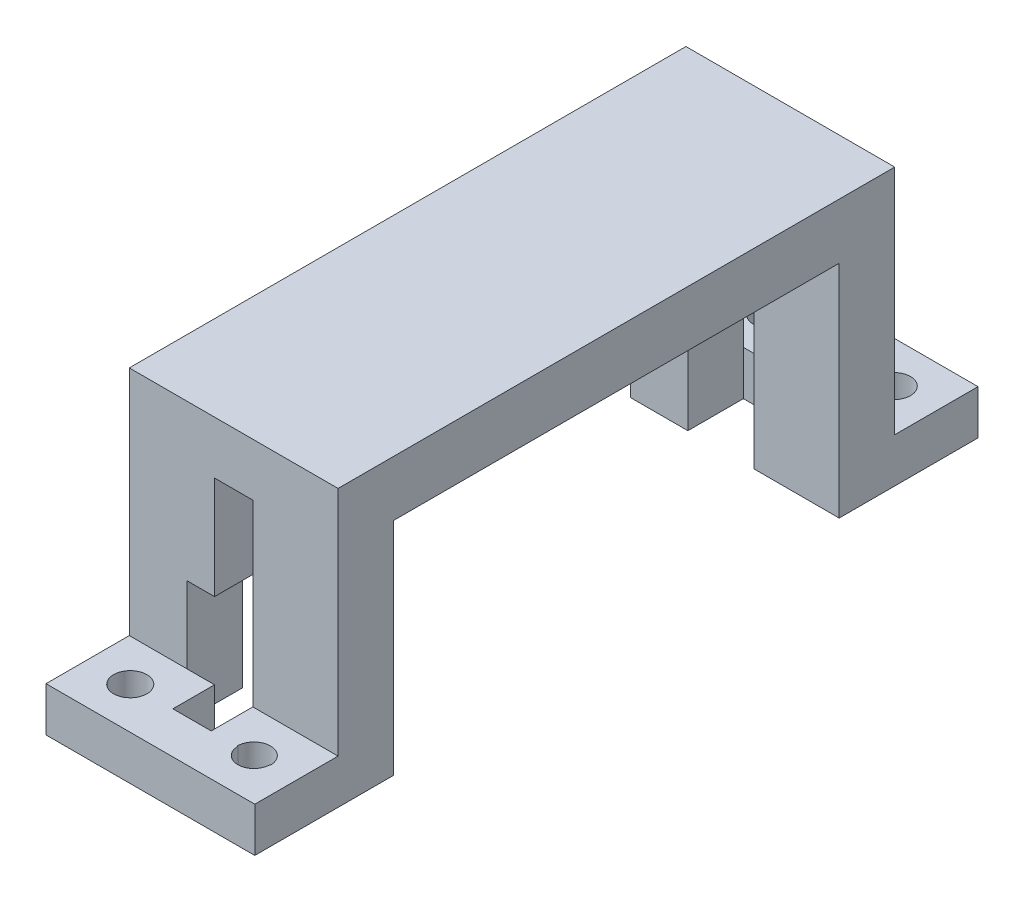
SolidWorks part; units mm, degrees
ref_plane "Front Plane" through (0, 0, 0) normal (0, 0, 1) x (1, 0, 0)
ref_plane "Top Plane" through (0, 0, 0) normal (0, 1, 0) x (1, 0, 0)
ref_plane "Right Plane" through (0, 0, 0) normal (1, 0, 0) x (0, 0, -1)
sketch "Sketch1" plane through (0, 0, 0) normal (1, 0, 0) x (0, 0, -1)
  line L0 (-25.0625, 0) -> (25.0625, 0)
  line L1 (-25.0625, 0) -> (-25.0625, -20.875)
  line L2 (-25.0625, -24.875) -> (-20.0625, -24.875)
  line L3 (-20.0625, -24.875) -> (-20.0625, -5)
  line L4 (-20.0625, -5) -> (20.0625, -5)
  line L5 (20.0625, -5) -> (20.0625, -24.875)
  line L6 (20.0625, -24.875) -> (25.0625, -24.875)
  line L7 (25.0625, -20.875) -> (25.0625, 0)
  line L8 (-20.0625, 0) -> (-20.0625, -5) construction
  line L10 (-25.0625, -24.875) -> (-32.5625, -24.875)
  line L12 (-25.0625, -20.875) -> (-32.5625, -20.875)
  line L13 (-32.5625, -24.875) -> (-32.5625, -20.875)
  line L14 (25.0625, -24.875) -> (32.5625, -24.875)
  line L16 (25.0625, -20.875) -> (32.5625, -20.875)
  line L17 (32.5625, -24.875) -> (32.5625, -20.875)
  point P4 (0, 0)
  dimension "D1" = 40.125
  dimension "D2" = 19.875
  dimension "D3" = 5
  dimension "D4" = 4
  dimension "D5" = 7.5
extrude "Boss-Extrude1" add sketch "Sketch1" along normal blind 18.8
sketch "Sketch2" plane through (0, 0, 32.5625) normal (0, 0, 1) x (1, 0, 0)
  line L0 (0, -24.875) -> (7.675, -24.875) construction
  line L1 (18.8, -24.875) -> (0, -24.875) construction
  line L2 (7.675, -24.875) -> (7.675, -4.75)
  line L3 (7.675, -4.75) -> (11.125, -4.75)
  line L4 (11.125, -4.75) -> (11.125, -24.875)
  line L5 (11.125, -24.875) -> (7.675, -24.875)
  dimension "D1" = 7.675
  dimension "D2" = 3.45
  dimension "D3" = 20.125
extrude "Cut-Extrude1" cut sketch "Sketch2" against normal through all
sketch "Sketch3" plane through (0, -20.875, 0) normal (0, 1, 0) x (1, 0, 0)
  line L0 (2.7647, -27.7641) -> (4.9103, -29.8609) construction
  line L1 (4.9103, -27.7641) -> (2.7647, -29.8609) construction
  line L2 (13.8897, -27.7641) -> (16.0353, -29.8609) construction
  line L3 (16.0353, -27.7641) -> (13.8897, -29.8609) construction
  line L4 (2.7647, 29.8609) -> (4.9103, 27.7641) construction
  line L5 (2.7647, 27.7641) -> (4.9103, 29.8609) construction
  line L6 (13.8897, 29.8609) -> (16.0353, 27.7641) construction
  line L7 (16.0353, 29.8609) -> (13.8897, 27.7641) construction
  circle A0 centre (3.8375, -28.8125) radius 1.5
  circle A2 centre (14.9625, -28.8125) radius 1.5
  circle A3 centre (14.9625, 28.8125) radius 1.5
  circle A4 centre (3.8375, 28.8125) radius 1.5
  dimension "D1" = 2
  dimension "D2" = 2
extrude "Cut-Extrude2" cut sketch "Sketch3" against normal up to next contours A0 | A2 | A3 | A4
sketch "Sketch4" plane through (7.675, 0, 0) normal (1, 0, 0) x (0, 0, -1)
  line L0 (-20.0625, -24.875) -> (-20.0625, -15.75)
  line L1 (-20.0625, -24.875) -> (-20.0625, -5) construction
  line L2 (-20.0625, -15.75) -> (-20.0625, -14)
  line L3 (-20.0625, -14) -> (-25.0625, -14)
  line L4 (-25.0625, 0) -> (-25.0625, -20.875) construction
  line L5 (-25.0625, -14) -> (-25.0625, -15.75)
  line L7 (-25.0625, -15.75) -> (-25.0625, -24.875)
  line L8 (-32.5625, -24.875) -> (-20.0625, -24.875) construction
  line L9 (-25.0625, -24.875) -> (-20.0625, -24.875)
  dimension "D1" = 9.125
  dimension "D2" = 1.75
sketch "Sketch7" plane through (7.675, 0, 0) normal (1, 0, 0) x (0, 0, -1)
  line L0 (-32.5625, -24.875) -> (-20.0625, -24.875) construction
  line L2 (-32.5625, -20.875) -> (-28.8125, -20.875)
  line L3 (-32.5625, -20.875) -> (-32.5625, -24.875)
  line L4 (-32.5625, -24.875) -> (-28.8125, -24.875)
  line L5 (-28.8125, -20.875) -> (-28.8125, -24.875)
  line L6 (-27.3125, -20.875) -> (-30.3125, -20.875) construction
extrude "Boss-Extrude2" add sketch "Sketch7" along normal up to next
mirror "Mirror1" about plane through (0, 0, 0) normal (0, 0, 1) of "Boss-Extrude2"
extrude "Cut-Extrude8" cut sketch "Sketch4" against normal blind 2.5
mirror "Mirror2" about plane through (0, 0, 0) normal (0, 0, 1) of "Cut-Extrude8", "Mirror1"
sketch "Sketch8" plane through (0, -20.875, 0) normal (0, 1, 0) x (1, 0, 0)
  line L0 (16.4625, 28.8125) -> (13.4625, 28.8125) construction
  line L1 (16.4625, -28.8125) -> (13.4625, -28.8125) construction
  circle A0 centre (14.9625, 28.8125) radius 1.5
  circle A1 centre (14.9625, -28.8125) radius 1.4357
extrude "Cut-Extrude9" cut sketch "Sketch8" against normal blind 2.5
